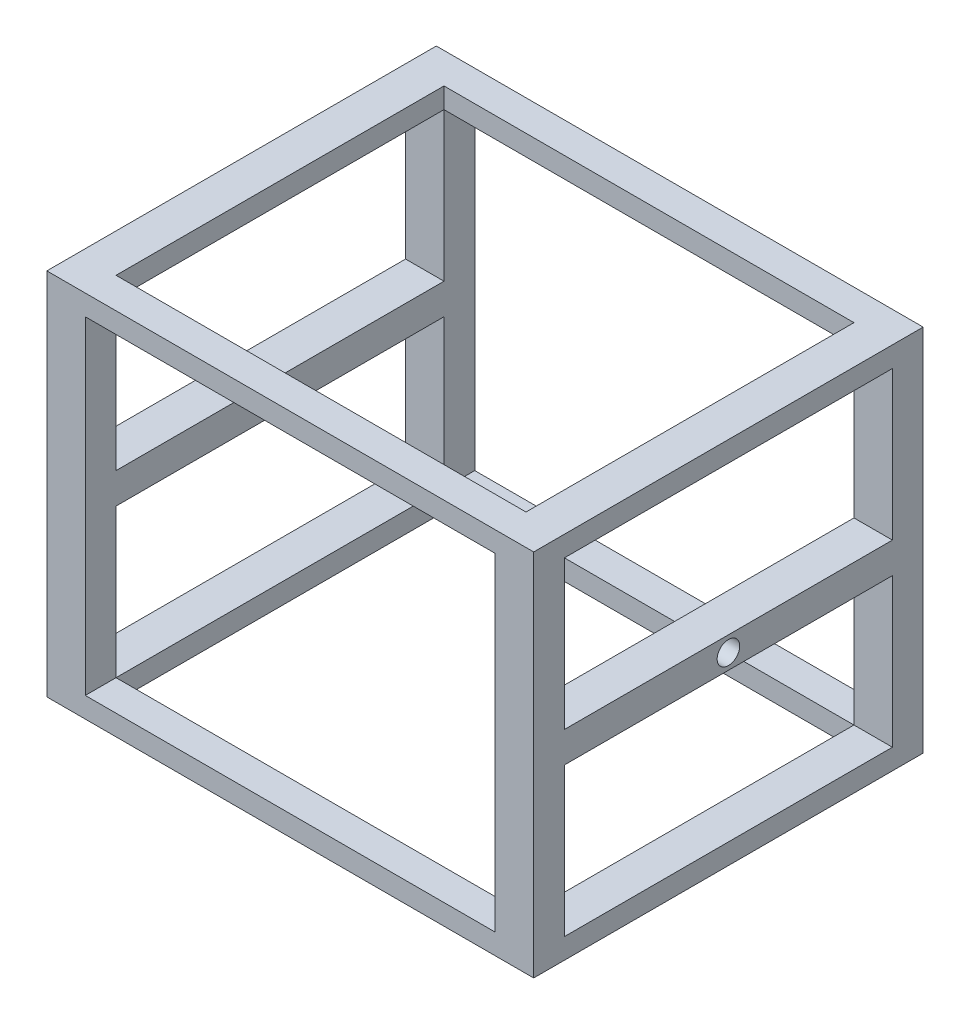
SolidWorks part; units mm, degrees
ref_plane "Front Plane" through (0, 0, 0) normal (0, 0, 1) x (1, 0, 0)
ref_plane "Top Plane" through (0, 0, 0) normal (0, 1, 0) x (1, 0, 0)
ref_plane "Right Plane" through (0, 0, 0) normal (1, 0, 0) x (0, 0, -1)
sketch "Sketch1" plane through (0, 0, 0) normal (0, 1, 0) x (1, 0, 0)
  line L1 (-593.75, 475) -> (593.75, 475)
  line L2 (-593.75, 475) -> (-593.75, -475)
  line L3 (-593.75, -475) -> (593.75, -475)
  line L4 (593.75, 475) -> (593.75, -475)
  line L5 (-593.75, 475) -> (593.75, -475) construction
  line L6 (-593.75, -475) -> (593.75, 475) construction
  line L7 (-500, 400) -> (500, 400)
  line L8 (-500, 400) -> (-500, -400)
  line L9 (-500, -400) -> (500, -400)
  line L10 (500, 400) -> (500, -400)
  line L11 (-500, 400) -> (500, -400) construction
  line L12 (-500, -400) -> (500, 400) construction
  point P0 (0, 0)
  point P6 (0, 0)
  dimension "D1" = 1000
  dimension "D2" = 800
  dimension "D3" = 950
extrude "Boss-Extrude1" add sketch "Sketch1" along normal blind 50
sketch "Sketch2" plane through (0, 50, 0) normal (0, 1, 0) x (1, 0, 0)
  line L0 (-500, 400) -> (-500, -400) construction
  line L1 (-593.75, 475) -> (-500, 475)
  line L2 (-593.75, 475) -> (-593.75, 400)
  line L3 (-593.75, 400) -> (-500, 400)
  line L4 (-500, 475) -> (-500, 400)
  line L6 (-500, -400) -> (-593.75, -400)
  line L7 (-500, -400) -> (-500, -475)
  line L8 (-500, -475) -> (-593.75, -475)
  line L9 (-593.75, -400) -> (-593.75, -475)
  line L10 (500, 400) -> (593.75, 400)
  line L11 (500, 400) -> (500, 475)
  line L12 (500, 475) -> (593.75, 475)
  line L13 (593.75, 400) -> (593.75, 475)
  line L14 (593.75, -475) -> (500, -475)
  line L15 (593.75, -475) -> (593.75, -400)
  line L16 (593.75, -400) -> (500, -400)
  line L17 (500, -475) -> (500, -400)
extrude "Boss-Extrude2" add sketch "Sketch2" along normal blind 800
ref_plane "Plane1" through (0, 450, 0) normal (0, 1, 0) x (1, 0, 0)
mirror "Mirror1" about plane through (0, 450, 0) normal (0, 1, 0) of "Boss-Extrude1"
sketch "Sketch3" plane through (593.75, 0, 0) normal (1, 0, 0) x (0, 0, -1)
  line L0 (-475, 900) -> (-475, 0) construction
  line L1 (-475, 487.5) -> (475, 487.5)
  line L2 (-475, 487.5) -> (-475, 412.5)
  line L3 (-475, 412.5) -> (475, 412.5)
  line L4 (475, 487.5) -> (475, 412.5)
  line L5 (475, 900) -> (475, 0) construction
  line L7 (-400, 850) -> (400, 850) construction
  dimension "D1" = 75
  dimension "D2" = 362.5
extrude "Boss-Extrude3" add sketch "Sketch3" against normal up to surface (93.75 mm away) up to face at (500, 450, 437.5)
sketch "Sketch4" plane through (-593.75, 0, 0) normal (-1, 0, 0) x (0, 0, 1)
  line L0 (41.25, 450) -> (-41.25, 450) construction
  line L1 (-475, 487.5) -> (475, 487.5)
  line L2 (-475, 487.5) -> (-475, 412.5)
  line L3 (-475, 412.5) -> (475, 412.5)
  line L4 (475, 487.5) -> (475, 412.5)
  line L5 (-475, 487.5) -> (475, 412.5) construction
  line L6 (-475, 412.5) -> (475, 487.5) construction
  point P0 (0, 450)
  dimension "D1" = 75
  dimension "D2" = 950
extrude "Boss-Extrude4" add sketch "Sketch4" against normal up to surface (93.75 mm away) up to face at (-500, 450, 437.5)
sketch "Sketch5" plane through (593.75, 0, 0) normal (1, 0, 0) x (0, 0, -1)
  line L0 (400, 487.5) -> (-400, 487.5) construction
  circle A0 centre (0, 450) radius 27.5
  dimension "D1" = 55
  dimension "D2" = 37.5
extrude "Cut-Extrude1" cut sketch "Sketch5" against normal blind 2000 and the other way blind 2000
